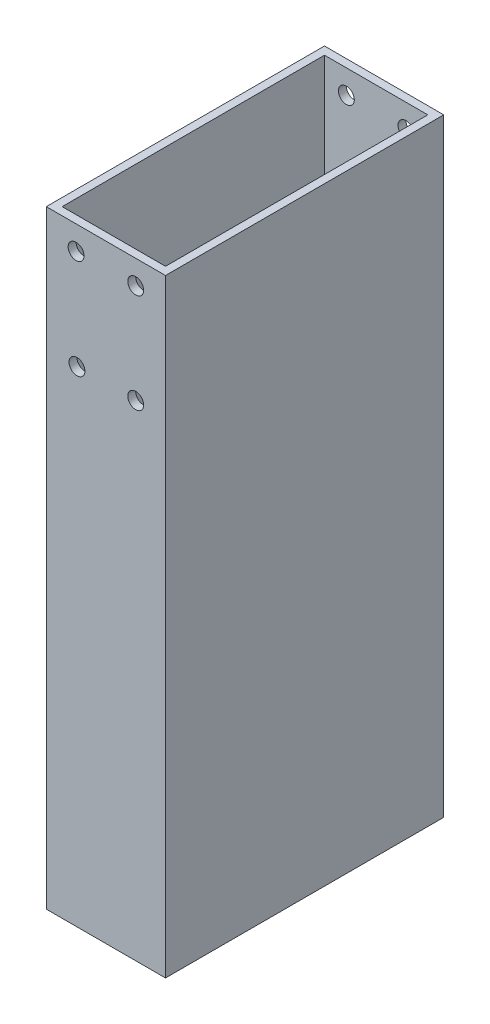
SolidWorks part; units mm, degrees
ref_plane "前视基准面" through (0, 0, 0) normal (0, 0, 1) x (1, 0, 0)
ref_plane "上视基准面" through (0, 0, 0) normal (0, 1, 0) x (1, 0, 0)
ref_plane "右视基准面" through (0, 0, 0) normal (1, 0, 0) x (0, 0, -1)
other "Configuration Table"
sketch "草图1" plane through (0, 0, 0) normal (0, 0, 1) x (1, 0, 0)
  line L1 (15, -383.07) -> (-15, -383.07)
  line L2 (15, -383.07) -> (15, 383.07)
  line L3 (15, 383.07) -> (-15, 383.07)
  line L4 (-15, -383.07) -> (-15, 383.07)
  line L5 (15, -383.07) -> (-15, 383.07) construction
  line L6 (15, 383.07) -> (-15, -383.07) construction
  circle A0 centre (-7.5, 377.0748) radius 2
  circle A1 centre (7.5, 377.0748) radius 2
  circle A2 centre (-7.2747, 352.0748) radius 2
  circle A3 centre (7.5, 352.0748) radius 2
  point P0 (0, 0)
  point P8 (-7.2747, 369.0727)
  point P12 (7.4312, 369.0727)
  point P16 (-7.2747, 345.686)
  point P20 (7.4312, 345.2481)
  point P21 (7.4312, 345.686)
  point P23 (-7.2747, 377.1427)
  point P24 (-7.999, 374.5017)
  point P26 (7.1929, 374.5017)
  point P28 (-7.999, 355.0254)
  point P30 (7.1929, 355.0254)
  point P32 (-7.2747, 377.1427)
  point P34 (7.4312, 377.1427)
  point P36 (-7.2747, 353.756)
  point P38 (7.4312, 353.756)
  dimension "D1" = 30
  dimension "D2" = 766.14
extrude "凸台-拉伸2" add sketch "草图1" along normal blind 70
sketch "草图2" plane through (0, -383.07, 0) normal (0, -1, 0) x (1, 0, 0)
  line L0 (-15, 70) -> (-15, 0) construction
  line L1 (-13, 68) -> (13, 68)
  line L2 (-13, 68) -> (-13, 2)
  line L3 (-13, 2) -> (13, 2)
  line L4 (13, 68) -> (13, 2)
  line L5 (-13, 68) -> (13, 2) construction
  line L6 (-13, 2) -> (13, 68) construction
  line L7 (-15, 70) -> (15, 70) construction
  line L8 (15, 70) -> (15, 0) construction
  line L9 (-15, 0) -> (15, 0) construction
  point P0 (0, 35)
  dimension "D1" = 2
  dimension "D2" = 2
  dimension "D3" = 2
  dimension "D4" = 2
extrude "切除-拉伸3" cut sketch "草图2" against normal through all contours L2 L1 L4 L3
sketch "草图3" plane through (0, 0, 70) normal (0, 0, 1) x (1, 0, 0)
  line L0 (-15, 230) -> (15, 230)
  line L1 (-15, 383.07) -> (-15, -383.07) construction
  line L2 (15, -383.07) -> (15, 383.07) construction
  line L3 (15, 383.07) -> (-15, 383.07) construction
  line L4 (-15, 230) -> (-15, -394.9368)
  line L5 (-15, -394.9368) -> (15, -394.9368)
  line L6 (15, -394.9368) -> (15, 230)
  dimension "D1" = 153.07
extrude "切除-拉伸4" cut sketch "草图3" against normal through all
